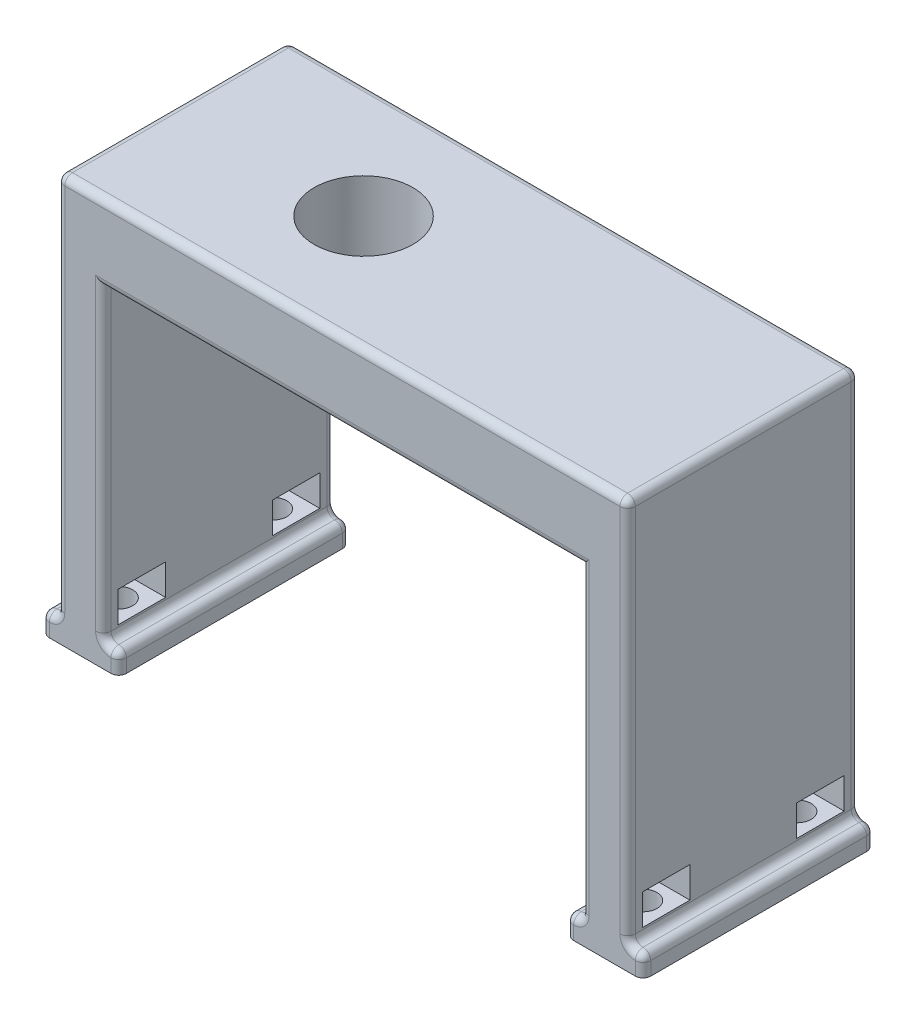
SolidWorks part; units mm, degrees
ref_plane "Front Plane" through (0, 0, 0) normal (0, 0, 1) x (1, 0, 0)
ref_plane "Top Plane" through (0, 0, 0) normal (0, 1, 0) x (1, 0, 0)
ref_plane "Right Plane" through (0, 0, 0) normal (1, 0, 0) x (0, 0, -1)
sketch "Sketch1" plane through (0, 0, 0) normal (0, 1, 0) x (1, 0, 0)
  line L1 (0, 0) -> (74, 0)
  line L2 (0, 0) -> (0, 30)
  line L3 (0, 30) -> (74, 30)
  line L4 (74, 0) -> (74, 30)
  dimension "D1" = 74
  dimension "D2" = 30
extrude "Boss-Extrude1" add sketch "Sketch1" along normal blind 10
sketch "Sketch2" plane through (0, 10, 0) normal (0, 1, 0) x (1, 0, 0)
  line L0 (0, 30) -> (0, 0) construction
  line L1 (74, 30) -> (0, 30) construction
  circle A0 centre (24.75, 15) radius 6.4
  dimension "D1" = 12.8
  dimension "D2" = 24.75
  dimension "D3" = 15
extrude "Cut-Extrude1" cut sketch "Sketch2" against normal blind 15
sketch "Sketch3" plane through (0, 0, 0) normal (0, 0, 1) x (1, 0, 0)
  line L0 (6, -40) -> (8, -40)
  line L1 (0, 0) -> (6, 0)
  line L2 (0, 0) -> (0, -40)
  line L4 (6, 0) -> (6, -40)
  line L5 (-2, -40) -> (0, -40)
  line L6 (-2, -40) -> (-2, -42.75)
  line L7 (-2, -42.75) -> (8, -42.75)
  line L8 (8, -40) -> (8, -42.75)
  dimension "D1" = 10
  dimension "D2" = 6
  dimension "D3" = 2
  dimension "D4" = 40
  dimension "D5" = 2.75
extrude "Boss-Extrude2" add sketch "Sketch3" against normal blind 30
hole_wizard "M3 Clearance Hole1" positions "Sketch7" profile "Sketch9" hole size "M3" standard "ANSI Metric"
sketch "Sketch7" plane through (0, -42.75, 0) normal (0, -1, 0) x (-1, 0, 0)
  line L0 (2, 0) -> (-8, 0) construction
  line L1 (2, 30) -> (-8, 30) construction
  line L2 (2, 30) -> (2, 0) construction
  point P0 (-3, 5)
  point P2 (-3, 25)
  dimension "D1" = 5
  dimension "D2" = 5
  dimension "D3" = 5
  dimension "D4" = 5
sketch "Sketch9" plane through (3, -42.75, -5) normal (1, 0, 0) x (0, 0, -1)
  line L0 (0, 0) -> (0, 11.0815)
  line L1 (0, 11.0815) -> (1.8, 10)
  line L2 (1.8, 10) -> (1.8, 0)
  line L5 (1.8, 0) -> (0, 0)
  line L10 (0, 11.0815) -> (-1.8, 10) construction
  line L11 (0, -6.35) -> (0, 107.95) construction
  dimension "Hole Dia." = 3.6
  dimension "Hole Depth" = 10
  dimension "Drill Angle" = 118
sketch "Sketch10" plane through (0, 0, 0) normal (-1, 0, 0) x (0, 0, 1)
  line L0 (0, 10) -> (0, -40) construction
  line L1 (-28.08, -34.75) -> (-21.92, -34.75)
  line L2 (-28.08, -34.75) -> (-28.08, -38.75)
  line L3 (-28.08, -38.75) -> (-21.92, -38.75)
  line L4 (-21.92, -34.75) -> (-21.92, -38.75)
  line L5 (-8.08, -34.75) -> (-1.92, -34.75)
  line L6 (-8.08, -34.75) -> (-8.08, -38.75)
  line L7 (-8.08, -38.75) -> (-1.92, -38.75)
  line L8 (-1.92, -34.75) -> (-1.92, -38.75)
  line L9 (-30, 10) -> (-30, -40) construction
  line L10 (-30, -42.75) -> (0, -42.75) construction
  dimension "D1" = 6.16
  dimension "D2" = 6.16
  dimension "D3" = 4
  dimension "D4" = 4
  dimension "D5" = 1.92
  dimension "D6" = 1.92
  dimension "D7" = 4
  dimension "D8" = 4
extrude "Cut-Extrude2" cut sketch "Sketch10" against normal up to next
ref_plane "Plane1" through (37, 0, 0) normal (-1, 0, 0) x (0, 0, 1)
mirror "Mirror1" about plane through (37, 0, 0) normal (-1, 0, 0) of "M3 Clearance Hole1", "Cut-Extrude2", "Boss-Extrude2"
fillet "Fillet1" radius 1 30 edges at (66, -41.375, 0) (76, -41.375, 0) (76, -40, -15) (74, -40, -15) (76, -41.375, -30) (66, -41.375, -30) (68, -40, -15) (66, -40, -15) (8, -41.375, 0) (8, -41.375, -30) (8, -40, -15) (6, -40, -15) (-2, -41.375, -30) (-2, -41.375, 0) (-2, -40, -15) (0, -40, -15) (74, -15, 0) (68, -20, 0) (37, 0, 0) (6, -20, 0) (0, -15, 0) (74, 10, -15) (37, 10, 0) (0, 10, -15) (68, -20, -30) (74, -15, -30) (0, -15, -30) (6, -20, -30) (37, 0, -30) (37, 10, -30)
